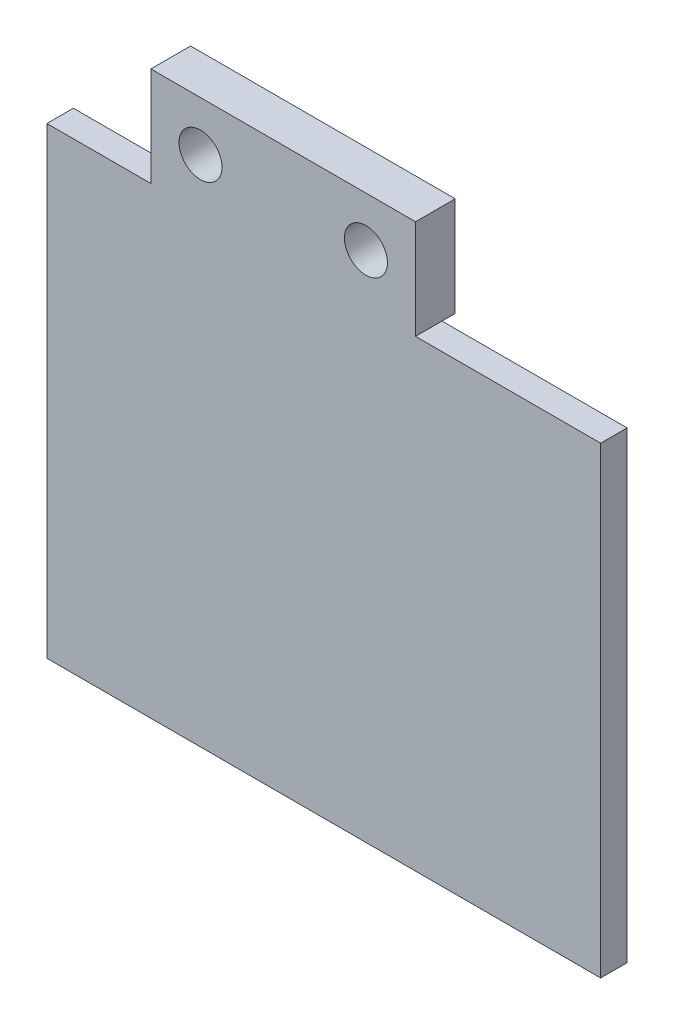
SolidWorks part; units mm, degrees
ref_plane "Front Plane" through (0, 0, 0) normal (0, 0, 1) x (1, 0, 0)
ref_plane "Top Plane" through (0, 0, 0) normal (0, 1, 0) x (1, 0, 0)
ref_plane "Right Plane" through (0, 0, 0) normal (1, 0, 0) x (0, 0, -1)
sketch "Sketch1" plane through (0, 0, 0) normal (0, 0, 1) x (1, 0, 0)
  line L0 (0, 0) -> (0, 35)
  line L1 (0, 35) -> (-7.5, 35)
  line L2 (-7.5, 35) -> (-7.5, 42.5)
  line L3 (-7.5, 42.5) -> (12.5, 42.5)
  line L4 (12.5, 42.5) -> (12.5, 35)
  line L5 (12.5, 35) -> (5, 35)
  line L6 (5, 35) -> (5, 0)
  line L7 (5, 0) -> (0, 0)
  circle A0 centre (-3.75, 38.75) radius 1.625
  circle A1 centre (8.75, 38.75) radius 1.625
  point P13 (12.5, 38.75)
  point P15 (-3.75, 35)
  point P17 (8.75, 35)
  dimension "D6" = 3.25
  dimension "D1" = 5
  dimension "D2" = 7.5
  dimension "D4" = 7.5
  dimension "D5" = 35
extrude "Boss-Extrude1" add sketch "Sketch1" along normal blind 3
sketch "Sketch2" plane through (0, 0, 3) normal (0, 0, -1) x (-1, 0, 0)
  line L0 (-5, 35) -> (-12.5, 35) construction
  line L1 (-26.4868, 35) -> (15.3577, 35)
  line L2 (-26.4868, 35) -> (-26.4868, 0)
  line L3 (-26.4868, 0) -> (15.3577, 0)
  line L4 (15.3577, 35) -> (15.3577, 0)
  line L5 (0, 0) -> (-5, 0) construction
extrude "Boss-Extrude2" add sketch "Sketch2" along normal offset from surface (2 mm away) 1 up to face at (-2.125, 38.75, 0)
